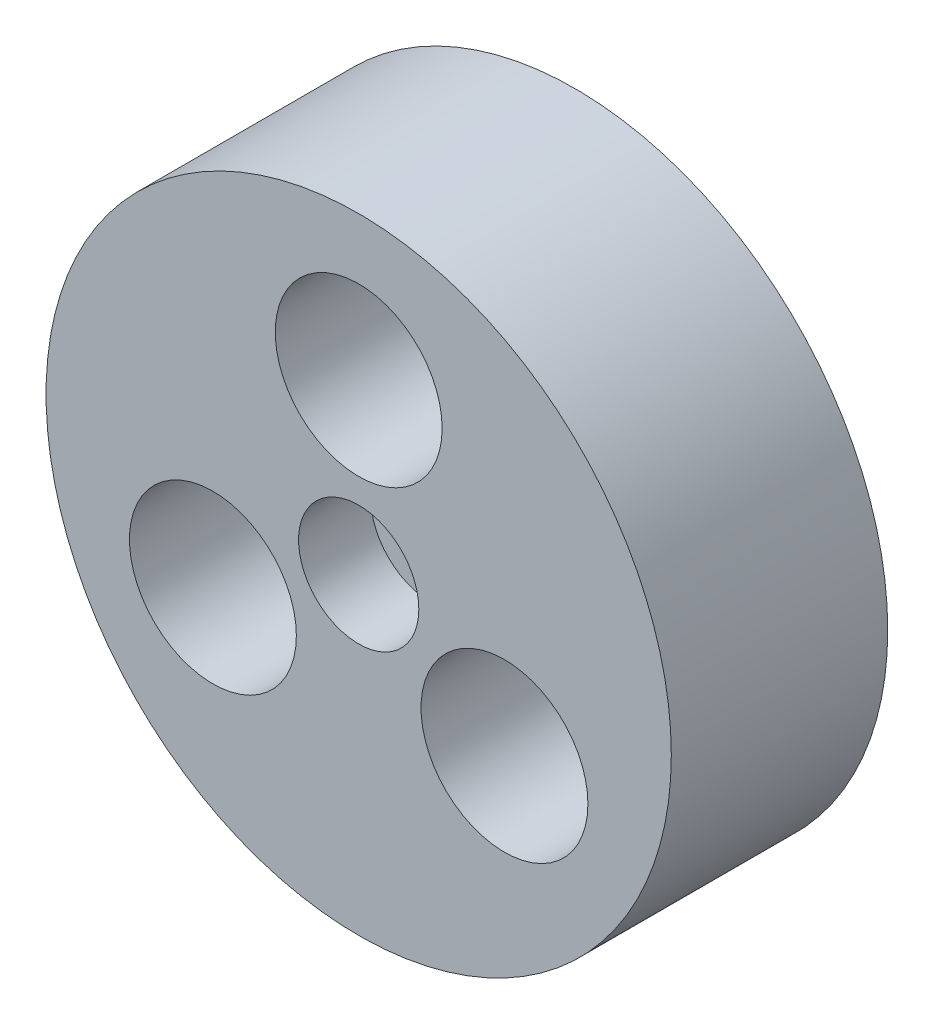
SolidWorks part; units mm, degrees
material "6061-T6 (SS)"
ref_plane "Front Plane" through (0, 0, 0) normal (0, 0, 1) x (1, 0, 0)
ref_plane "Top Plane" through (0, 0, 0) normal (0, 1, 0) x (1, 0, 0)
ref_plane "Right Plane" through (0, 0, 0) normal (1, 0, 0) x (0, 0, -1)
sketch "Sketch1" plane through (0, 0, 0) normal (0, 0, 1) x (1, 0, 0)
  circle A0 centre (0, 0) radius 13
  dimension "D1" = 26
extrude "Boss-Extrude1" add sketch "Sketch1" along normal blind 4
sketch "Sketch5" plane through (0, 0, 4) normal (0, 0, 1) x (1, 0, 0)
  point P4 (0, 7)
  point P11 (6.0622, -3.5)
  point P12 (-6.0622, -3.5)
  dimension "D2" = 3
hole_wizard "CSK for M3 Hex Socket Countersunk Head Screw1" positions "Sketch5" profile "Sketch7" countersink size "M3" standard "DIN"
sketch "Sketch7" plane through (0, 7, 4) normal (1, 0, 0) x (0, -1, 0)
  line L0 (0, 0) -> (0, 13.0215)
  line L1 (0, 13.0215) -> (1.7, 12)
  line L2 (1.7, 12) -> (1.7, 1.77)
  line L3 (1.7, 1.77) -> (3.47, 0)
  line L5 (3.47, 0) -> (0, 0)
  line L6 (-1.7, 1.77) -> (-3.47, 0) construction
  line L10 (0, 13.0215) -> (-1.7, 12) construction
  line L11 (0, -6.35) -> (0, 107.95) construction
  dimension "Hole Dia." = 3.4
  dimension "Hole Depth" = 12
  dimension "Near C'Sink Dia." = 6.94
  dimension "Near C'Sink Angle" = 90
  dimension "Drill Angle" = 118
sketch "Sketch8" plane through (0, 0, 4) normal (0, 0, 1) x (1, 0, 0)
  circle A0 centre (-6.0622, -3.5) radius 3.47 construction
  circle A1 centre (0, 0) radius 13
  circle A2 centre (0, 0) radius 13
  circle A3 centre (6.0622, -3.5) radius 3.47 construction
  circle A4 centre (0, 7) radius 3.47 construction
  circle A5 centre (-6.0622, -3.5) radius 3.47
  circle A6 centre (6.0622, -3.5) radius 3.47
  circle A7 centre (0, 7) radius 3.47
  dimension "D1" = 0
extrude "Boss-Extrude2" add sketch "Sketch8" along normal blind 5
sketch "Sketch9" plane through (0, 0, 9) normal (0, 0, 1) x (1, 0, 0)
  circle A0 centre (0, 0) radius 2.5
  dimension "D1" = 5
extrude "Cut-Extrude1" cut sketch "Sketch9" against normal blind 3
